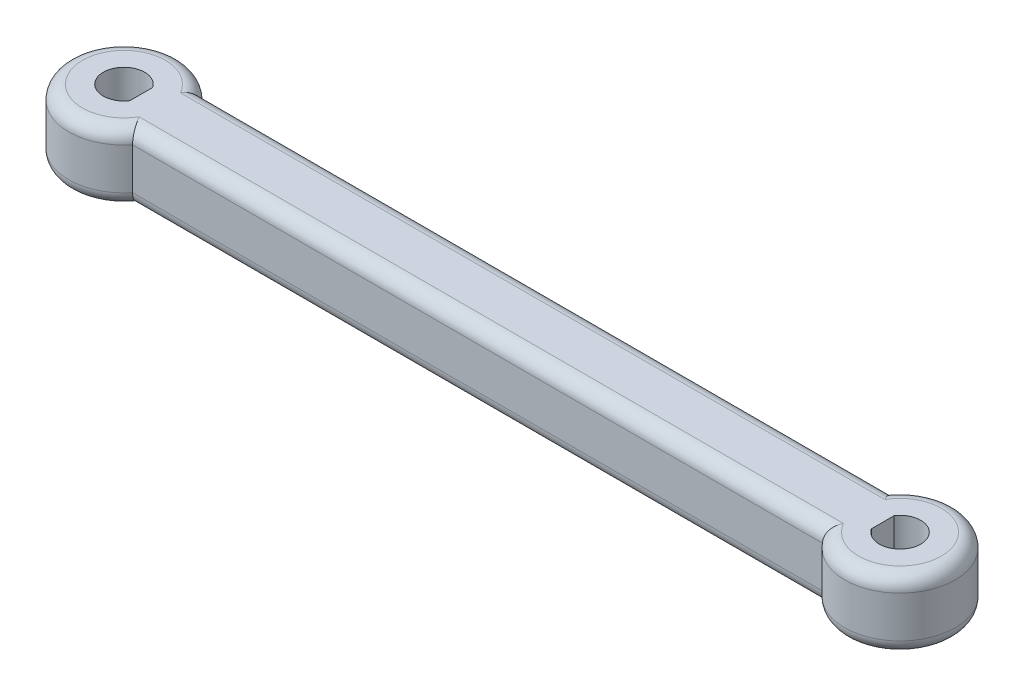
SolidWorks part; units mm, degrees
ref_plane "Plano frontal" through (0, 0, 0) normal (0, 0, 1) x (1, 0, 0)
ref_plane "Plano superior" through (0, 0, 0) normal (0, 1, 0) x (1, 0, 0)
ref_plane "Plano direito" through (0, 0, 0) normal (1, 0, 0) x (0, 0, -1)
sketch "Esboço1" plane through (0, 0, 0) normal (0, 1, 0) x (1, 0, 0)
  line L2 (6.245, 5) -> (106.245, 5)
  line L3 (6.245, -5) -> (106.245, -5)
  line L4 (2.5001, 1.6582) -> (0, 0) construction
  line L5 (0, 0) -> (2.5001, -1.6582) construction
  line L6 (-3.7598, 0) -> (4.2446, 0) construction
  line L7 (2.5001, 1.6582) -> (2.5001, -1.6582)
  line L8 (56.245, 14.4945) -> (56.245, -12.8649) construction
  line L9 (109.9899, 1.6582) -> (109.9899, -1.6582)
  arc A0 (2.5001, 1.6582) -> (2.5001, -1.6582) centre (0, 0) ccw
  arc A4 (6.245, 5) -> (6.245, -5) centre (0, 0) ccw
  arc A5 (106.245, -5) -> (106.245, 5) centre (112.49, 0) ccw
  arc A6 (109.9899, 1.6582) -> (109.9899, -1.6582) centre (112.49, 0) cw
  dimension "D1" = 6
  dimension "D2" = 16
  dimension "D3" = 16
  dimension "D4" = 100
  dimension "D5" = 67.11
  dimension "D6" = 33.555
  dimension "D7" = 5
  dimension "D8" = 5
extrude "Ressalto-extrusão1" add sketch "Esboço1" along normal blind 10
fillet "Filete1" radius 2 8 edges at (120.49, 0, 0) (56.245, 0, 5) (-8, 0, 0) (56.245, 0, -5) (120.49, 10, 0) (56.245, 10, 5) (56.245, 10, -5) (-8, 10, 0)
